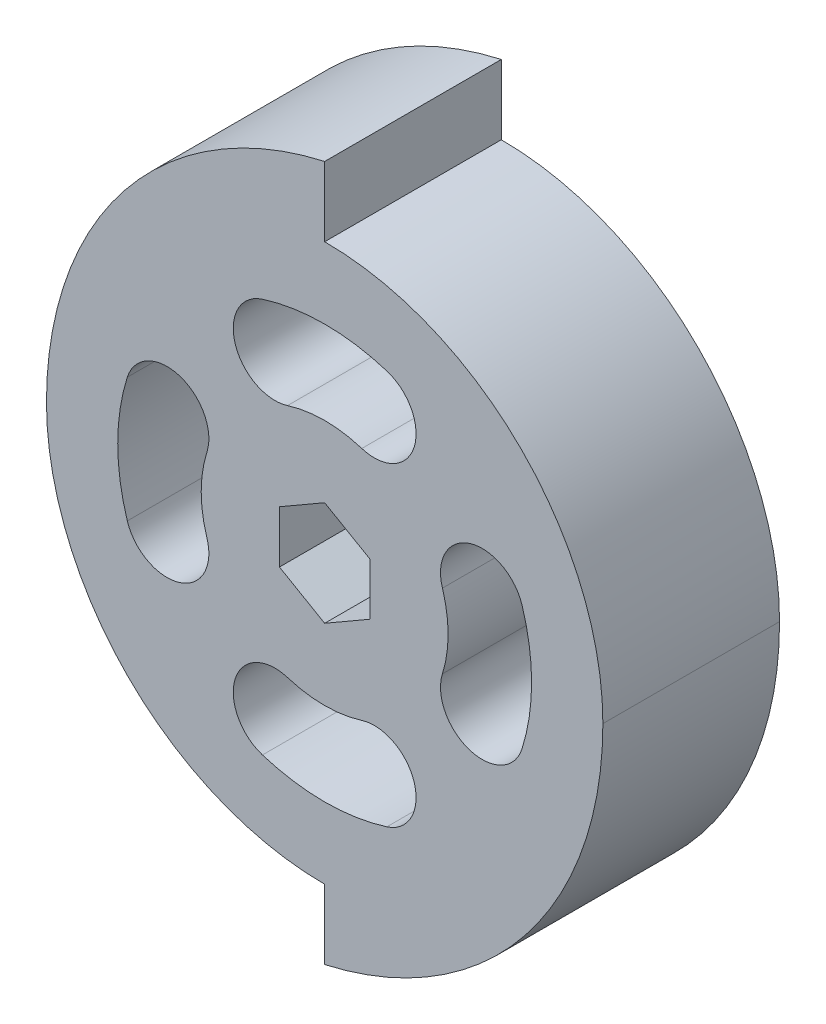
SolidWorks part; units mm, degrees
material "AR500"
ref_plane "Front Plane" through (0, 0, 0) normal (0, 0, 1) x (1, 0, 0)
ref_plane "Top Plane" through (0, 0, 0) normal (0, 1, 0) x (1, 0, 0)
ref_plane "Right Plane" through (0, 0, 0) normal (1, 0, 0) x (0, 0, -1)
sketch "Sketch3" plane through (0, 0, 0) normal (0, 0, 1) x (1, 0, 0)
  line L5 (0, 20) -> (0, 25)
  line L6 (3.25, -1.8764) -> (3.25, 1.8764)
  line L7 (3.25, 1.8764) -> (0, 3.7528)
  line L8 (0, 3.7528) -> (-3.25, 1.8764)
  line L9 (-3.25, 1.8764) -> (-3.25, -1.8764)
  line L10 (-3.25, -1.8764) -> (0, -3.7528)
  line L11 (0, -3.7528) -> (3.25, -1.8764)
  line L12 (0, -20) -> (0, -25)
  circle A2 centre (0, 0) radius 20 construction
  circle A3 centre (0, 0) radius 3.25 construction
  arc A9 (0, 25) -> (-20, 0) centre (5.625, 0) ccw
  arc A10 (0, 20) -> (-20, 0) centre (0, 0) cw construction
  arc A11 (0, -25) -> (20, 0) centre (-5.625, 0) ccw
  arc A12 (0, 20) -> (20, 0) centre (0, 0) cw
  arc A13 (0, -20) -> (-20, 0) centre (0, 0) cw
  point P3 (0, 0)
  point P25 (0, 0)
  dimension "D2" = 5
  dimension "D1" = 40
  dimension "D3" = 6.5
extrude "Boss-Extrude1" add sketch "Sketch3" along normal blind 12.7
sketch "Sketch4" plane through (0, 0, 12.7) normal (0, 0, 1) x (1, 0, 0)
  line L0 (0, 20) -> (0, 3.7528) construction
  line L1 (-3.5713, 11.3267) -> (0, 0) construction
  line L2 (0, 0) -> (3.5713, 11.3267) construction
  circle A0 centre (0, 0) radius 11.8764 construction
  circle A2 centre (-3.5713, 11.3267) radius 3 construction
  circle A3 centre (3.5713, 11.3267) radius 3 construction
  arc A4 (-4.4734, 14.1879) -> (4.4734, 14.1879) centre (0, 0) cw
  arc A5 (2.6692, 8.4656) -> (-2.6692, 8.4656) centre (0, 0) ccw
  circle A6 centre (0, 11.8764) radius 3 construction
  arc A7 (-4.4734, 14.1879) -> (-2.6692, 8.4656) centre (-3.5713, 11.3267) ccw
  arc A8 (2.6692, 8.4656) -> (4.4734, 14.1879) centre (3.5713, 11.3267) ccw
  point P5 (0, 11.8764)
  point P6 (0, 0)
  point P7 (0, 20)
  point P10 (0, 20)
  dimension "D2" = 3
  dimension "D1" = 35
extrude "Cut-Extrude1" cut sketch "Sketch4" against normal through all
ref_axis "Axis1" through (0, 0, -0.475) along (0, 0, 1)
pattern_circular "CirPattern1" count 4 over 360 about axis through (0, 0, -0.475) along (0, 0, 1) of "Cut-Extrude1"
